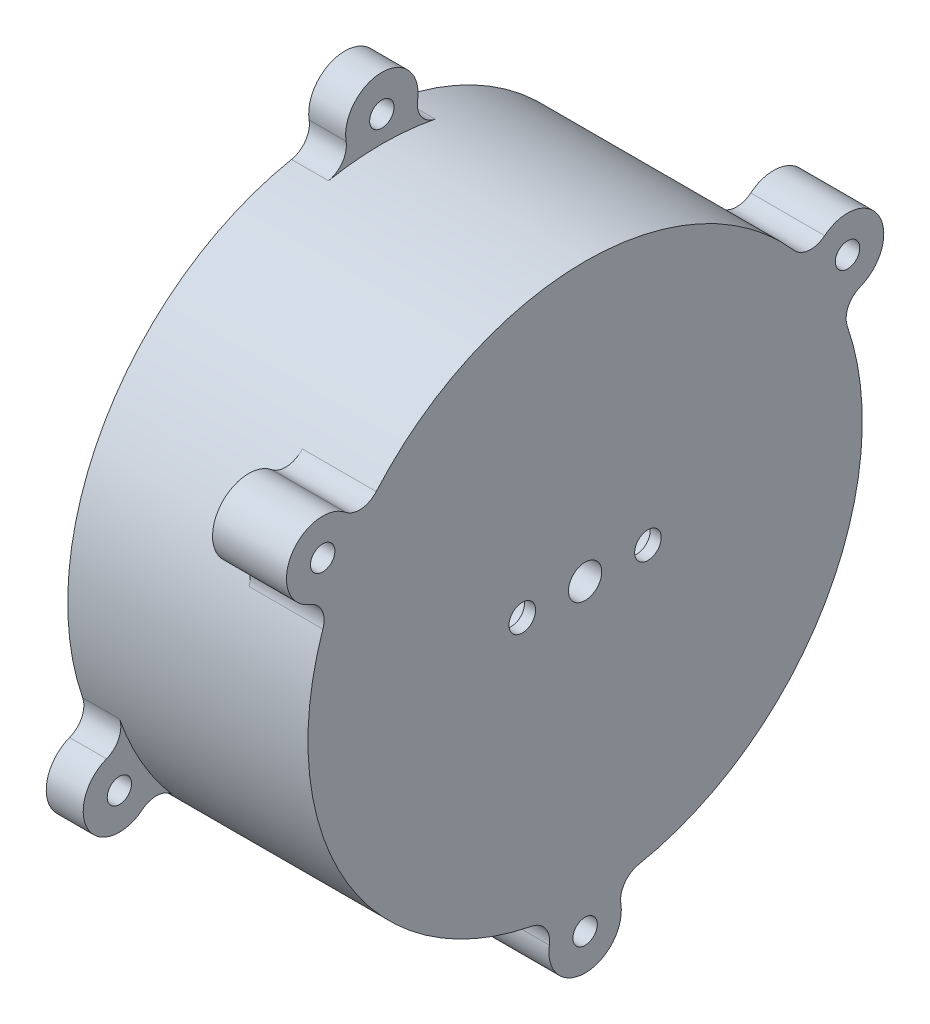
SolidWorks part; units mm, degrees
ref_plane "Plane1" through (0, 0, 0) normal (0, 0, 1) x (1, 0, 0)
ref_plane "Plane2" through (0, 0, 0) normal (0, 1, 0) x (1, 0, 0)
ref_plane "Plane3" through (0, 0, 0) normal (1, 0, 0) x (0, 0, -1)
sketch "HoldingSke" plane through (0, 0, 0) normal (0, 1, 0) x (1, 0, 0)
  line L0 (0, 0) -> (0.4589, -0.6553)
  line L1 (-15, 0) -> (100, 0) construction
  line L2 (0, 0) -> (-2.1039, 2.3779)
  line L3 (0, 0) -> (-11.863, 4.5341)
  line L4 (0, 0) -> (4.9534, 7.0742)
  line L5 (0, 0) -> (-23.7986, -8.8762)
  line L6 (0, 0) -> (-10.5278, -7.1032)
  line L7 (-2.1039, 2.3779) -> (3.3635, 27.1825)
  line L8 (-76.2, 3.6279) -> (-54.61, 3.6279)
  line L9 (-67.7845, 28.3722) -> (-49.3413, 33.142)
  line L10 (-76.2, 71.12) -> (104.1128, 71.12)
  line L11 (0, 0) -> (-28, 0)
  line L12 (-76.2, 101.6) -> (-76.155, 101.6)
  line L13 (24.9733, 27.94) -> (52.9518, 28.4284)
  line L14 (24.9733, 27.94) -> (24.9743, 27.94)
  line L15 (24.9733, 27.94) -> (100.4006, 29.5858)
  circle A0 centre (0, 0) radius 37.5
  circle A1 centre (0, 0) radius 12.7
  circle A2 centre (0, 0) radius 12.7
  dimension "Num_teeth" = 55
  dimension "Pitch_radius" = 180.3128
  dimension "Width" = 28
  dimension "Diameter" = 75
sketch "BasProSke" plane through (0, 0, 0) normal (0, 1, 0) x (1, 0, 0)
  line L0 (-10, 0) -> (60, 0) construction
  line L1 (0, 33.125) -> (0, 37.5)
  line L2 (0, 33.125) -> (28, 33.125)
  line L3 (28, 33.125) -> (28, 37.5)
  line L4 (28, 37.5) -> (0, 37.5)
  dimension "Thickness" = 28
  dimension "Diameter" = 75
revolve "Base-Revolve" add sketch "BasProSke" angle 360 about L0
sketch "TooCutSke" plane through (0, 0, 0) normal (1, 0, 0) x (0, 0, -1)
  line L3 (1.0941, 34.3576) -> (1.0941, 53.6633) construction
  line L4 (0, 0) -> (0, 59.563) construction
  line L5 (0, 0) -> (-3.9007, 68.2161) construction
  line L6 (-15.2783, 29.1274) -> (36.0712, 32.0636) construction
  circle A0 centre (0, 0) radius 34.375 construction
  circle A1 centre (0, 0) radius 35.9385 construction
  circle A2 centre (0, 0) radius 29.9521 construction
  circle A3 centre (0, 0) radius 33.0996 construction
  arc A4 (1.4514, 33.0678) -> (0.5036, 35.935) centre (-15.2783, 29.1274) ccw
  arc A5 (1.4514, 33.0678) -> (-1.4514, 33.0678) centre (0, 0) ccw
  arc A6 (0.5036, 35.935) -> (-0.5036, 35.935) centre (0, 0) ccw
  arc A7 (-0.5036, 35.935) -> (-1.4514, 33.0678) centre (15.2783, 29.1274) ccw
extrude "ToothCut" cut sketch "TooCutSke" along normal through all
fillet "Breaks" [suppressed] radius 0.125
fillet "RootFillets" [suppressed] radius 0.3135
pattern_circular "TeethCuts" count 55 every 6.545 about axis through (-10, 0, 0) along (1, 0, 0) of "RootFillets", "Breaks", "ToothCut"
sketch "Sketch1" plane through (28, 0, 0) normal (1, 0, 0) x (0, 0, -1)
  circle A0 centre (0, 0) radius 37.5
extrude "Boss-Extrude1" add sketch "Sketch1" along normal blind 4.5
sketch "Sketch2" plane through (32.5, 0, 0) normal (1, 0, 0) x (0, 0, -1)
  circle A0 centre (0, 0) radius 2.25
  circle A1 centre (-8.5, 0) radius 1.8
  circle A2 centre (8.5, 0) radius 1.8
  dimension "D1" = 4.5
  dimension "D2" = 3.6
  dimension "D3" = 8.5
  dimension "D4" = 8.5
extrude "Cut-Extrude1" cut sketch "Sketch2" against normal blind 4.5
sketch "Sketch3" plane through (28, 0, 0) normal (-1, 0, 0) x (0, 0, 1)
  circle A0 centre (-8.5, 0) radius 3.25
  circle A1 centre (8.5, 0) radius 3.25
  dimension "D1" = 6.5
extrude "Cut-Extrude2" cut sketch "Sketch3" against normal blind 3
sketch "Sketch4" plane through (0, 0, 0) normal (-1, 0, 0) x (0, 0, 1)
  line L0 (0, 0) -> (0, 45.9) construction
  circle A0 centre (0, 41) radius 1.65
  circle A1 centre (0, 0) radius 2.25 construction
  circle A2 centre (35.507, -20.5) radius 1.65
  circle A3 centre (-35.507, -20.5) radius 1.65
  arc A4 (-3.2765, 37.3566) -> (3.2765, 37.3566) centre (0, 41) cw
  circle A5 centre (0, 0) radius 37.5 construction
  arc A6 (-3.2765, 37.3566) -> (3.2765, 37.3566) centre (0, 0) cw
  arc A7 (33.99, -15.8408) -> (30.7135, -21.5158) centre (35.507, -20.5) cw
  arc A8 (33.99, -15.8408) -> (30.7135, -21.5158) centre (0, 0) cw
  arc A9 (-30.7135, -21.5158) -> (-33.99, -15.8408) centre (-35.507, -20.5) cw
  arc A10 (-30.7135, -21.5158) -> (-33.99, -15.8408) centre (0, 0) cw
  point P11 (0, 0)
  point P28 (0, 0)
  dimension "D1" = 3.3
  dimension "D2" = 41
  dimension "D5" = 3
  dimension "D4" = 45.9
  dimension "D3" = 3
extrude "Boss-Extrude2" add sketch "Sketch4" against normal blind 5
fillet "Fillet1" radius 3 6 edges at (2.5, -21.5158, -30.7135) (2.5, -21.5158, 30.7135) (2.5, -15.8408, 33.99) (2.5, 37.3566, 3.2765) (2.5, -15.8408, -33.99) (2.5, 37.3566, -3.2765)
sketch "Sketch5" plane through (32.5, 0, 0) normal (1, 0, 0) x (0, 0, -1)
  line L0 (0, 0) -> (35.507, 20.5) construction
  line L1 (0, 0) -> (0, 41) construction
  circle A1 centre (35.507, 20.5) radius 1.65
  circle A2 centre (0, -41) radius 1.65
  circle A3 centre (-35.507, 20.5) radius 1.65
  arc A4 (33.99, 15.8408) -> (30.7135, 21.5158) centre (35.507, 20.5) ccw
  circle A5 centre (0, 0) radius 37.5 construction
  arc A6 (30.7135, 21.5158) -> (33.99, 15.8408) centre (0, 0) cw
  arc A7 (-3.2765, -37.3566) -> (3.2765, -37.3566) centre (0, -41) ccw
  arc A8 (3.2765, -37.3566) -> (-3.2765, -37.3566) centre (0, 0) cw
  arc A9 (-30.7135, 21.5158) -> (-33.99, 15.8408) centre (-35.507, 20.5) ccw
  arc A10 (-33.99, 15.8408) -> (-30.7135, 21.5158) centre (0, 0) cw
  point P13 (0, 0)
  point P26 (0, 0)
  dimension "D2" = 3.3
  dimension "D4" = 3
  dimension "D1" = 60
  dimension "D3" = 3
extrude "Boss-Extrude3" add sketch "Sketch5" against normal blind 10
fillet "Fillet2" radius 3 6 edges at (27.5, 15.8408, 33.99) (27.5, -37.3566, 3.2765) (27.5, -37.3566, -3.2765) (27.5, 21.5158, 30.7135) (27.5, 15.8408, -33.99) (27.5, 21.5158, -30.7135)
equation "' \"Module@HoldingSke\" = 6.35"
equation "' \"Num_teeth@HoldingSke\" = 24"
equation "' \"Ap@HoldingSke\" =  14.5"
equation "' \"Ap@HoldingSke\" = 14.5"
equation "' \"Width@HoldingSke\" = 12"
equation "' \"Diameter@HoldingSke\" = 8 * 25.4"
equation "' \"Show_teeth@HoldingSke\" = 100"
equation "' \"Backlash@HoldingSke\" = 0.009 * 25.4"
equation "' \"Addendum_fac@HoldingSke\" = 1.0"
equation "' \"Dedendum_fac@HoldingSke\" = 1.25"
equation "' \"Dedendum_add@HoldingSke\" = 0.00005 * 25.4"
equation "' \"Clearance_fac@HoldingSke\" = 0.25"
equation "\"Pitch@HoldingSke\" = 1 / \"Module@HoldingSke\" "
equation "\"Overcut_dia@TooCutSke\" = (\"Num_teeth@HoldingSke\" - 2 * \"Addendum_fac@HoldingSke\") / \"Pitch@HoldingSke\" - 0.002 * 25.4"
equation "\"Pitch_dia@TooCutSke\" = \"Num_teeth@HoldingSke\" / \"Pitch@HoldingSke\""
equation "\"Base_dia@TooCutSke\" = \"Num_teeth@HoldingSke\" / \"Pitch@HoldingSke\" * cos((\"Ap@HoldingSke\"  * 3.14159265 / 180)) * 0.90"
equation "\"Root_dia@TooCutSke\" = \"Num_teeth@HoldingSke\"  / \"Pitch@HoldingSke\" + 2 *  \"Dedendum_fac@HoldingSke\"/ \"Pitch@HoldingSke\" + \"Dedendum_add@HoldingSke\" * 2"
equation "\"Half_ang@TooCutSke\" = 180 / \"Num_teeth@HoldingSke\""
equation "\"Half_CT@TooCutSke\" = \"Num_teeth@HoldingSke\" / \"Pitch@HoldingSke\" * sin((3.14159265 / 2 / \"Num_teeth@HoldingSke\")) / 2 + 10 * \"Backlash@HoldingSke\" / 4"
equation "\"Flank_rad@TooCutSke\" = \"Num_teeth@HoldingSke\" / \"Pitch@HoldingSke\" / 4"
equation "\"Radius@RootFillets\"= \"Clearance_fac@HoldingSke\" / \"Pitch@HoldingSke\" + \"Dedendum_add@HoldingSke\""
equation "\"Break_rad@Breaks\" = 0.02 / \"Pitch@HoldingSke\" * 5"
equation "\"Num_teeth@TeethCuts\" = int( \"Show_teeth@HoldingSke\" ) + 1"
equation "\"Num_teeth@TeethCuts\" = ((sgn( \"Num_teeth@TeethCuts\" - \"Num_teeth@HoldingSke\" )-1)*( \"Num_teeth@TeethCuts\" - \"Num_teeth@HoldingSke\" ))/-2+ \"Num_teeth@HoldingSke\""
equation "\"Num_teeth@TeethCuts\" = ((sgn( \"Num_teeth@TeethCuts\" - 2.0)+1)*( \"Num_teeth@TeethCuts\" - 2.0))/2 +2.0"
equation "\"Angle@TeethCuts\" = 360.0 / \"Num_teeth@HoldingSke\""
equation "\"Diameter@BasProSke\" = \"Num_teeth@HoldingSke\"  / \"Pitch@HoldingSke\" + 2 *  \"Dedendum_fac@HoldingSke\"/ \"Pitch@HoldingSke\" + \"Dedendum_add@HoldingSke\" * 2 + 0.002 * 25.4"
equation "\"Diameter@BasProSke\" = ((sgn( \"Diameter@BasProSke\"  - \"Diameter@HoldingSke\" )+1)*( \"Diameter@BasProSke\"  - \"Diameter@HoldingSke\" ))/2 + \"Diameter@HoldingSke\""
equation "\"Inside_diameter@BasProSke\" =  (\"Num_teeth@HoldingSke\" - 2 * \"Addendum_fac@HoldingSke\") / \"Pitch@HoldingSke\" "
equation "\"Thickness@BasProSke\"  = \"Width@HoldingSke\""
